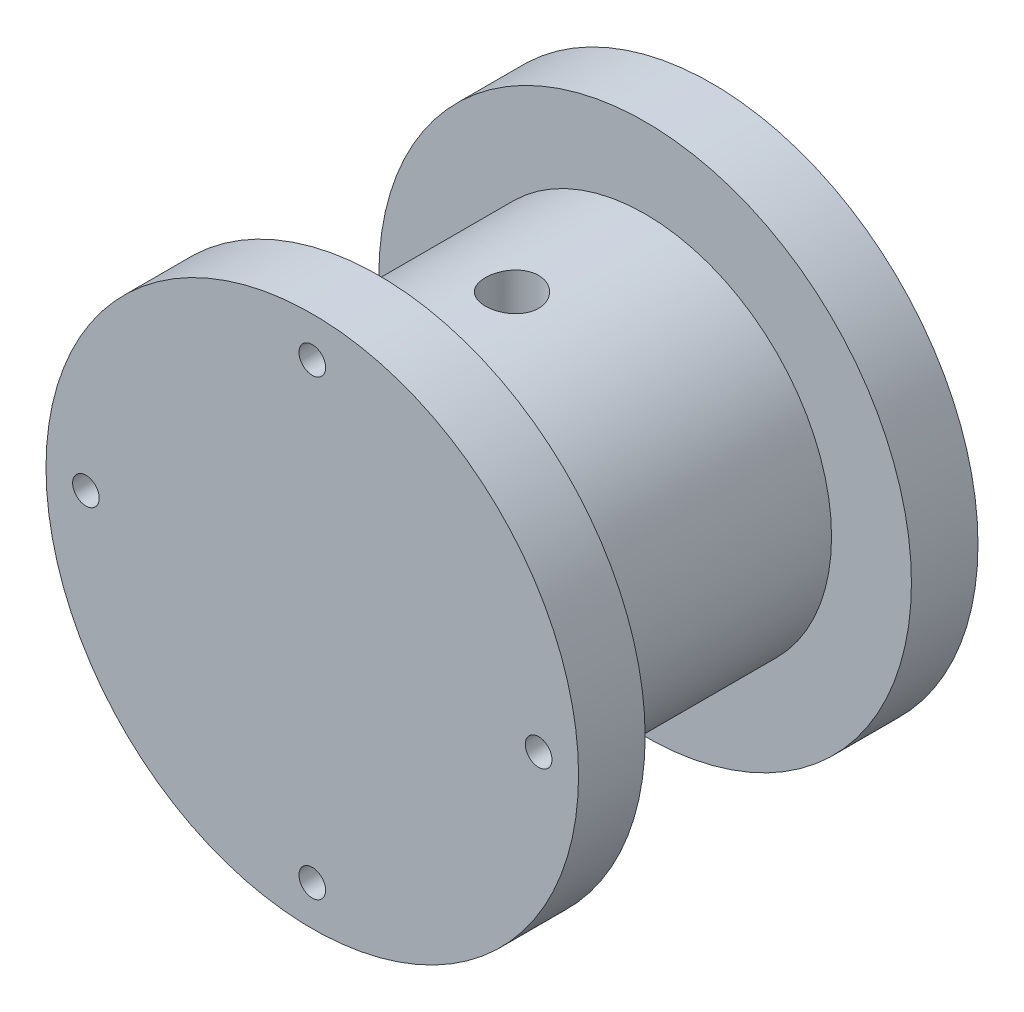
SolidWorks part; units mm, degrees
ref_plane "Front Plane" through (0, 0, 0) normal (0, 0, 1) x (1, 0, 0)
ref_plane "Top Plane" through (0, 0, 0) normal (0, 1, 0) x (1, 0, 0)
ref_plane "Right Plane" through (0, 0, 0) normal (1, 0, 0) x (0, 0, -1)
sketch "Sketch1" plane through (0, 0, 0) normal (0, 0, 1) x (1, 0, 0)
  circle A0 centre (0, 0) radius 14
  dimension "D1" = 28
extrude "Boss-Extrude1" add sketch "Sketch1" along normal blind 10 and the other way blind 10
sketch "Sketch3" plane through (0, 0, 10) normal (0, 0, 1) x (1, 0, 0)
  circle A0 centre (0, 0) radius 20
  dimension "D1" = 40
extrude "Boss-Extrude2" add sketch "Sketch3" along normal blind 5
mirror "Mirror1" about plane through (0, 0, 0) normal (0, 0, 1) of "Boss-Extrude2"
ref_plane "Plane1" through (0, 5, 0) normal (0, 1, 0) x (1, 0, 0)
sketch "Sketch4" plane through (0, 5, 0) normal (0, 1, 0) x (1, 0, 0)
  circle A0 centre (0, 0) radius 2
  dimension "D1" = 4
extrude "Cut-Extrude1" cut sketch "Sketch4" against normal through all and the other way through all contours A0
sketch "Sketch5" plane through (0, 0, 10) normal (0, 0, -1) x (-1, 0, 0)
  line L1 (0, 16.5) -> (0, -16.5) construction
  circle A0 centre (0, 17) radius 1
  circle A1 centre (0, 0) radius 20 construction
  dimension "D1" = 2
  dimension "D2" = 17
extrude "Cut-Extrude2" cut sketch "Sketch5" against normal through all
pattern_circular "CirPattern1" count 4 over 360 about axis through (0, 0, -10) along (0, 0, 1) of "Cut-Extrude2" reverse direction yes
sketch "Sketch6" plane through (0, 0, -15) normal (0, 0, -1) x (-1, 0, 0)
  circle A0 centre (0, 0) radius 3
  dimension "D1" = 6
extrude "Boss-Extrude3" add sketch "Sketch6" along normal blind 7
